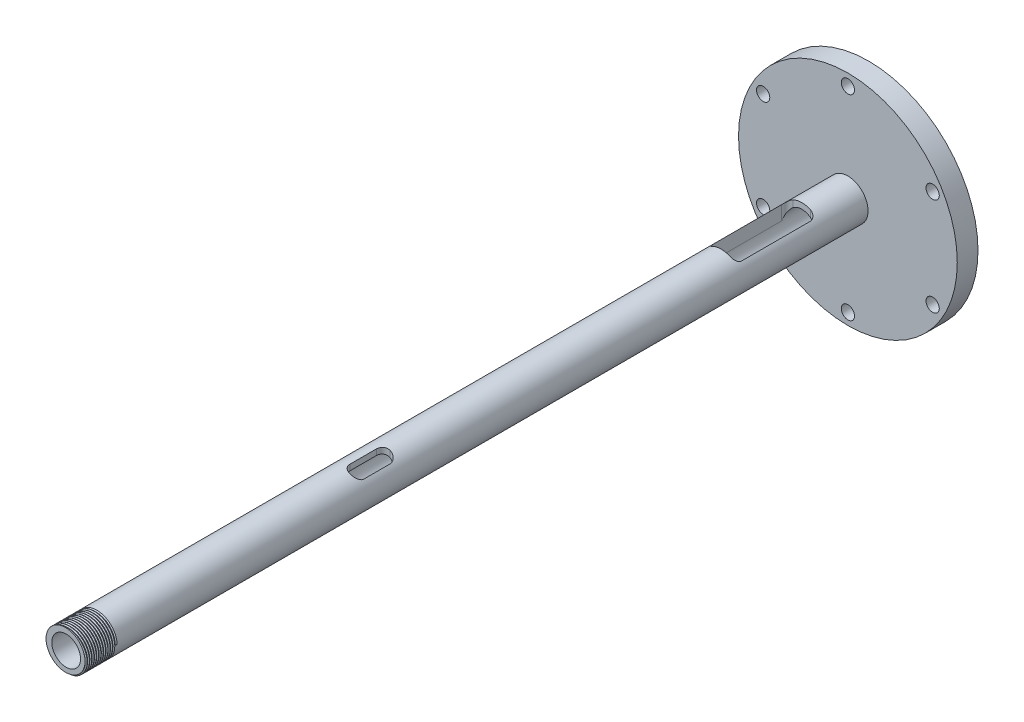
SolidWorks part; units mm, degrees
ref_plane "Front" through (0, 0, 0) normal (0, 0, 1) x (1, 0, 0)
ref_plane "Top" through (0, 0, 0) normal (0, 1, 0) x (1, 0, 0)
ref_plane "Right" through (0, 0, 0) normal (1, 0, 0) x (0, 0, -1)
sketch "Sketch1" plane through (0, 0, 0) normal (0, 0, 1) x (1, 0, 0)
  circle A0 centre (0, 0) radius 17.5
  circle A1 centre (0, 0) radius 12.5
  dimension "D1" = 35
  dimension "D2" = 25
extrude "Boss-Extrude1" add sketch "Sketch1" along normal blind 700
sketch "Sketch2" plane through (0, 0, 0) normal (0, 0, -1) x (-1, 0, 0)
  circle A0 centre (0, 0) radius 72.5
  circle A1 centre (0, 0) radius 12.5 construction
  circle A2 centre (0, 0) radius 12.5
  dimension "D1" = 145
extrude "Boss-Extrude2" add sketch "Sketch2" against normal blind 3
sketch "Sketch3" plane through (0, 0, 3) normal (0, 0, 1) x (1, 0, 0)
  circle A0 centre (0, 0) radius 95
  circle A1 centre (0, 0) radius 17.5 construction
  circle A2 centre (0, 0) radius 17.5
  dimension "D1" = 190
extrude "Boss-Extrude3" add sketch "Sketch3" along normal blind 18
sketch "Sketch4" plane through (0, 0, 3) normal (0, 0, -1) x (-1, 0, 0)
  line L0 (0, 0) -> (0, 85) construction
  circle A0 centre (0, 0) radius 85 construction
  circle A1 centre (0, 85) radius 5.75
  dimension "D1" = 170
  dimension "D2" = 11.5
extrude "Cut-Extrude1" cut sketch "Sketch4" against normal up to next
pattern_circular "CirPattern1" count 6 over 360 about axis through (0, 0, 21) along (0, 0, 1) of "Cut-Extrude1"
sketch "Sketch5" plane through (0, 0, 0) normal (0, 1, 0) x (1, 0, 0)
  line L0 (0, 0) -> (0, -61) construction
  line L1 (-12.5, -61) -> (12.5, -61)
  line L2 (-12.5, -61) -> (-12.5, -131)
  line L3 (-12.5, -131) -> (12.5, -131)
  line L4 (12.5, -61) -> (12.5, -131)
  line L5 (-12.5, -61) -> (12.5, -131) construction
  line L6 (-12.5, -131) -> (12.5, -61) construction
  line L7 (-17.5, -21) -> (17.5, -21) construction
  point P0 (0, -96)
  dimension "D1" = 25
  dimension "D2" = 40
  dimension "D3" = 70
extrude "Cut-Extrude2" cut sketch "Sketch5" along normal up to next
fillet "Fillet1" radius 5 4 edges at (-12.5, 6.1237, 131) (12.5, 6.1237, 131) (12.5, 6.1237, 61) (-12.5, 6.1237, 61)
sketch "Sketch7" plane through (0, 0, 0) normal (0, 1, 0) x (1, 0, 0)
  line L0 (-17.5, -700) -> (17.5, -700) construction
  line L1 (12.5, -460) -> (0.5, -460)
  line L2 (12.5, -460) -> (12.5, -425)
  line L3 (12.5, -425) -> (0.5, -425)
  line L4 (0.5, -460) -> (0.5, -425)
  line L5 (12.5, -460) -> (0.5, -425) construction
  line L6 (12.5, -425) -> (0.5, -460) construction
  line L7 (12.5, -126) -> (12.5, -66) construction
  point P4 (6.5, -442.5)
  dimension "D1" = 240
  dimension "D2" = 35
  dimension "D3" = 12
extrude "Cut-Extrude3" cut sketch "Sketch7" along normal up to next
fillet "Fillet2" radius 6 4 edges at (0.5, 14.9914, 460) (12.5, 6.1237, 460) (12.5, 6.1237, 425) (0.5, 14.9914, 425)
thread "Thread1" pitch 2 method cut profile "Thread Profile1" start angle 0, offset 2, length 27, pitch 2, diameter 35
ref_plane "Plane1" through (-17.5, 0, 702) normal (0, -1, 0) x (-1, 0, 0)
sketch "Thread Profile1" plane through (-17.5, 0, 702) normal (0, -1, 0) x (-1, 0, 0)
  line L0 (0, 0) -> (0, 2) construction
  line L11 (0, 0) -> (0, 1.75)
  line L12 (0, 1.75) -> (-1.0825, 1.125)
  line L13 (-1.0825, 1.125) -> (-1.0825, 0.625)
  line L15 (-1.0825, 0.625) -> (0, 0)
  line L17 (-1.0825, 0.875) -> (0, 0.875) construction
  point P2 (0, 0)
  dimension "Pitch" = 2
  dimension "Profile_Angle" = 60
  dimension "Profile_Land" = 0.5
  dimension "Profile_Height" = 1.0825
